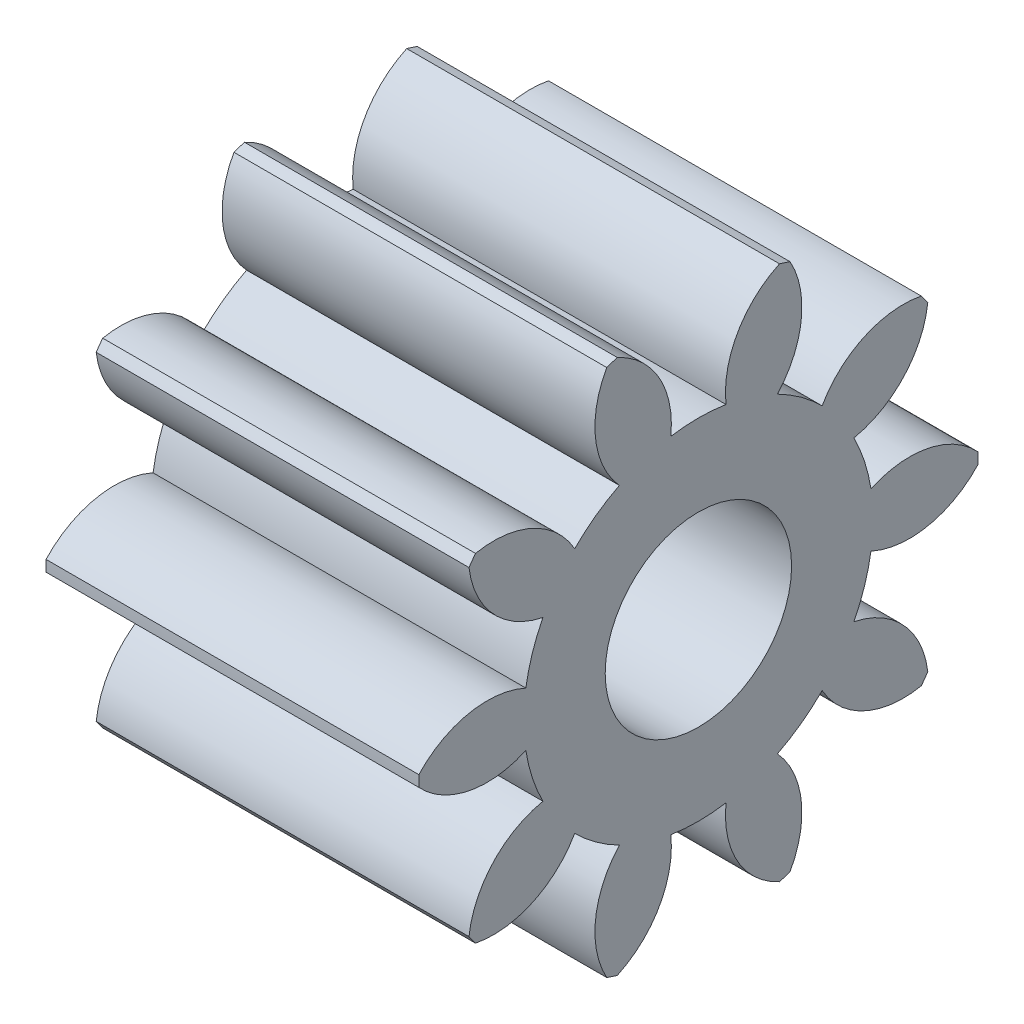
SolidWorks part; units mm, degrees
ref_plane "Plane1" through (0, 0, 0) normal (0, 0, 1) x (1, 0, 0)
ref_plane "Plane2" through (0, 0, 0) normal (0, 1, 0) x (1, 0, 0)
ref_plane "Plane3" through (0, 0, 0) normal (1, 0, 0) x (0, 0, -1)
sketch "HoldingSke" plane through (0, 0, 0) normal (0, 1, 0) x (1, 0, 0)
  line L0 (0, 0) -> (1.9696, -0.3473)
  line L1 (-15, 0) -> (100, 0) construction
  line L2 (0, 0) -> (-2.1039, 2.3779)
  line L3 (0, 0) -> (-11.863, 4.5341)
  line L4 (0, 0) -> (8.5048, 1.4996)
  line L5 (0, 0) -> (-46.8476, -17.4728)
  line L6 (0, 0) -> (-2.9014, -1.9576)
  line L7 (-2.1039, 2.3779) -> (8.6586, 51.2059)
  line L8 (-76.2, 54.61) -> (-75.9, 54.61)
  line L9 (-71.009, 38.7566) -> (-53.1078, 45.2721)
  line L10 (-76.2, 71.12) -> (104.1128, 71.12)
  line L11 (0, 0) -> (-3.5, 0)
  line L12 (-76.2, 101.6) -> (-76.181, 101.6)
  line L13 (24.9733, 27.94) -> (52.9518, 28.4284)
  line L14 (24.9733, 27.94) -> (24.9743, 27.94)
  line L15 (24.9733, 27.94) -> (100.4006, 29.5858)
  line L16 (-63.627, -0.5) -> (-12.827, -0.5)
  circle A0 centre (0, 0) radius 1
  circle A1 centre (0, 0) radius 1.874
  circle A2 centre (0, 0) radius 37.5
  circle A3 centre (0, 0) radius 1
  dimension "Num_teeth" = 10
  dimension "Pitch_radius" = 180.3128
  dimension "Width" = 3.5
sketch "BasProSke" plane through (0, 0, 0) normal (0, 1, 0) x (1, 0, 0)
  line L0 (-10, 0) -> (60, 0) construction
  line L1 (0, 0) -> (0, 3)
  line L2 (0, 0) -> (4, 0)
  line L3 (4, 0) -> (4, 3)
  line L4 (4, 3) -> (0, 3)
  dimension "Thickness" = 4
  dimension "Diameter" = 6
revolve "Base-Revolve" add sketch "BasProSke" angle 360 about L0
sketch "TooCutSke" plane through (0, 0, 0) normal (1, 0, 0) x (0, 0, -1)
  line L1 (0, 0) -> (0, 107) construction
  line L2 (0, 0) -> (-0.4243, 2.4637) construction
  line L3 (0, 0) -> (-1.5292, 4.7063) construction
  line L4 (-0.4243, 2.4637) -> (-0.7646, 2.3532) construction
  arc A0 (0.2964, 1.8504) -> (-0.2964, 1.8504) centre (0, 0) ccw
  arc A1 (0.9059, 2.8866) -> (-0.9059, 2.8866) centre (0, 0) ccw
  circle A2 centre (0, 0) radius 2.5 construction
  circle A3 centre (0, 0) radius 2.3492 construction
  arc A4 (-0.2964, 1.8504) -> (-0.9059, 2.8866) centre (-1.2901, 1.9633) ccw
  arc A5 (0.9059, 2.8866) -> (0.2964, 1.8504) centre (1.2901, 1.9633) ccw
extrude "ToothCut" cut sketch "TooCutSke" along normal through all
fillet "Breaks" [suppressed] radius 0.01 tangent propagation no
fillet "RootFillets" [suppressed] radius 0.126
pattern_circular "TeethCuts" count 10 every 36 about axis through (-10, 0, 0) along (1, 0, 0) of "ToothCut", "RootFillets", "Breaks"
sketch "HubNeaOneSke" plane through (0, 0, 0) normal (-1, 0, 0) x (0, 0, 1)
  circle A0 centre (0, 0) radius 1.874
  dimension "Diameter" = 3.748
extrude "HubNearOne" [suppressed] add sketch "HubNeaOneSke" along normal blind 46.0001
sketch "HubNeaBotSke" plane through (0, 0, 0) normal (-1, 0, 0) x (0, 0, 1)
  circle A0 centre (0, 0) radius 1.874
  dimension "Diameter" = 3.748
extrude "HubNearBoth" [suppressed] add sketch "HubNeaBotSke" along normal blind 23
ref_plane "FarPln" through (4, 0, 0) normal (1, 0, 0) x (0, 0, -1)
sketch "HubFarSke" plane through (4, 0, 0) normal (1, 0, 0) x (0, 0, -1)
  circle A0 centre (0, 0) radius 1.874
  dimension "Diameter" = 3.748
extrude "HubFar" [suppressed] add sketch "HubFarSke" along normal blind 23
sketch "BorSke" plane through (0, 0, 0) normal (1, 0, 0) x (0, 0, -1)
  circle A0 centre (0, 0) radius 1
  dimension "Diameter" = 2
extrude "Bore" cut sketch "BorSke" along normal mid plane 100.0001
sketch "KeySke" plane through (0, 0, 0) normal (1, 0, 0) x (0, 0, -1)
  line L0 (-0.4, 0) -> (-0.4, 1.3)
  line L1 (-0.4, 1.3) -> (0.4, 1.3)
  line L2 (0.4, 1.3) -> (0.4, 0)
  line L3 (0, 0) -> (0, 34) construction
  line L4 (-0.4, 0) -> (0.4, 0)
  dimension "Width" = 0.8
extrude "Keyway" [suppressed] cut sketch "KeySke" along normal mid plane 100.0001
pattern_circular "Keyway2" [suppressed] count 2 every 90 about axis through (-10, 0, 0) along (1, 0, 0) reverse direction yes
equation "' \"Module@HoldingSke\" = 6.35"
equation "' \"Num_teeth@HoldingSke\" = 12"
equation "' \"Ap@HoldingSke\" =  20"
equation "' \"Ap@HoldingSke\" = 20"
equation "' \"Width@HoldingSke\" = 0.5 * 25.4"
equation "' \"Hub_dia@HoldingSke\"= 1 * 25.4"
equation "' \"Hub_dia@HoldingSke\" = 1 * 25.4"
equation "' \"Overall_len@HoldingSke\" = 1.0 * 25.4"
equation "' \"Bore@HoldingSke\" = 0.75 * 25.4"
equation "' \"T_dim@HoldingSke\" = 0.1 * 25.4"
equation "' \"Width@KeySke\" = 0.25 * 25.4"
equation "' \"Show_teeth@HoldingSke\" = 13"
equation "' \"Backlash@HoldingSke\" = 0.009 * 25.4"
equation "' \"Addendum_fac@HoldingSke\" = 1.0"
equation "' \"Dedendum_fac@HoldingSke\" = 1.25"
equation "' \"Dedendum_add@HoldingSke\" = 0.00005 * 25.4"
equation "' \"Clearance_fac@HoldingSke\" = 0.25"
equation "\"Pitch@HoldingSke\" = 1 / \"Module@HoldingSke\""
equation "\"Overcut_dia@TooCutSke\" = (\"Num_teeth@HoldingSke\" + 2 * \"Addendum_fac@HoldingSke\") / \"Pitch@HoldingSke\" + 0.002 * 25.4"
equation "\"Pitch_dia@TooCutSke\" = \"Num_teeth@HoldingSke\" / \"Pitch@HoldingSke\""
equation "\"Base_dia@TooCutSke\" = \"Num_teeth@HoldingSke\" / \"Pitch@HoldingSke\" * cos((\"Ap@HoldingSke\"  * 3.14159265 / 180))"
equation "\"Root_dia@TooCutSke\" = (\"Num_teeth@HoldingSke\" + 2) / \"Pitch@HoldingSke\" - 2 * (\"Addendum_fac@HoldingSke\" + \"Dedendum_fac@HoldingSke\") / \"Pitch@HoldingSke\" - \"Dedendum_add@HoldingSke\" * 2"
equation "\"Half_ang@TooCutSke\" = 180 / \"Num_teeth@HoldingSke\""
equation "\"Half_CT@TooCutSke\" = \"Num_teeth@HoldingSke\" / \"Pitch@HoldingSke\" * sin((3.14159265 / 2 / \"Num_teeth@HoldingSke\")) / 2 - 7 * \"Backlash@HoldingSke\" / 4"
equation "\"Flank_rad@TooCutSke\" = \"Num_teeth@HoldingSke\" / \"Pitch@HoldingSke\" / 5"
equation "\"Radius@RootFillets\" = \"Clearance_fac@HoldingSke\" / \"Pitch@HoldingSke\" + \"Dedendum_add@HoldingSke\""
equation "\"Break_rad@Breaks\" = 0.02 / \"Pitch@HoldingSke\""
equation "\"Thickness@HoldingSke\" = \"Width@HoldingSke\""
equation "\"OAL@HoldingSke\" = \"Thickness@HoldingSke\""
equation "\"MHD@HoldingSke\" = (\"Num_teeth@HoldingSke\" + 2) / \"Pitch@HoldingSke\" - 2 * (\"Addendum_fac@HoldingSke\" + \"Dedendum_fac@HoldingSke\")  / \"Pitch@HoldingSke\" - \"Dedendum_add@HoldingSke\" * 2"
equation "\"MBD@HoldingSke\" = (\"Num_teeth@HoldingSke\" + 2) / \"Pitch@HoldingSke\" - 2 * (\"Addendum_fac@HoldingSke\" + \"Dedendum_fac@HoldingSke\")  / \"Pitch@HoldingSke\" - \"Dedendum_add@HoldingSke\" * 2 - 0.002 * 25.4"
equation "\"MHD@HoldingSke\" = ((sgn( \"MHD@HoldingSke\" - \"Hub_dia@HoldingSke\" )-1)*( \"MHD@HoldingSke\" - \"Hub_dia@HoldingSke\" ))/-2+ \"Hub_dia@HoldingSke\""
equation "\"MBD@HoldingSke\" = ((sgn( \"MBD@HoldingSke\" - \"Bore@HoldingSke\" )-1)*( \"MBD@HoldingSke\" - \"Bore@HoldingSke\" ))/-2+ \"Bore@HoldingSke\""
equation "\"OAL@HoldingSke\" = ((sgn( \"OAL@HoldingSke\" - \"Overall_len@HoldingSke\" )+1)*( \"OAL@HoldingSke\" - \"Overall_len@HoldingSke\" ))/2 + \"Overall_len@HoldingSke\" + 0.000002 * 25.4"
equation "\"Num_teeth@TeethCuts\" = int( \"Show_teeth@HoldingSke\" ) + 1"
equation "\"Num_teeth@TeethCuts\" = ((sgn( \"Num_teeth@TeethCuts\" - \"Num_teeth@HoldingSke\" )-1)*( \"Num_teeth@TeethCuts\" - \"Num_teeth@HoldingSke\" ))/-2+ \"Num_teeth@HoldingSke\""
equation "\"Num_teeth@TeethCuts\" = ((sgn( \"Num_teeth@TeethCuts\" - 2.0)+1)*( \"Num_teeth@TeethCuts\" - 2.0))/2 +2.0"
equation "\"Angle@TeethCuts\" = 360.0 / \"Num_teeth@HoldingSke\""
equation "\"Diameter@BasProSke\" = (\"Num_teeth@HoldingSke\" + 2 * \"Addendum_fac@HoldingSke\") / \"Pitch@HoldingSke\""
equation "\"Thickness@BasProSke\"=\"Thickness@HoldingSke\"+0.5"
equation "' \"Fillet_rad@BasProSke\" =  \"Thickness@HoldingSke\" * 0.05"
equation "' \"Fillet_rad@BasProSke\" = \"Thickness@HoldingSke\" * 0.05"
equation "\"MHD@HoldingSke\" = ((sgn( \"MHD@HoldingSke\" - \"Root_dia@TooCutSke\" )-1)*( \"MHD@HoldingSke\" - \"Root_dia@TooCutSke\" ))/-2+ \"Root_dia@TooCutSke\""
equation "\"Diameter@HubNeaOneSke\" = \"MHD@HoldingSke\""
equation "\"Length@HubNearOne\" = \"OAL@HoldingSke\" - \"Thickness@BasProSke\""
equation "\"Diameter@HubNeaBotSke\" = \"MHD@HoldingSke\""
equation "\"Length@HubNearBoth\" = ( \"OAL@HoldingSke\" - \"Thickness@BasProSke\" ) / 2.0"
equation "\"Thickness@FarPln\" = \"Thickness@BasProSke\""
equation "\"Diameter@HubFarSke\" = \"MHD@HoldingSke\""
equation "\"Length@HubFar\" = ( \"OAL@HoldingSke\" - \"Thickness@BasProSke\" ) / 2.0"
equation "\"Diameter@BorSke\" = \"MBD@HoldingSke\""
equation "\"D1@Bore\" = \"OAL@HoldingSke\" * 2.0"
equation "\"D1@Keyway\" = \"OAL@HoldingSke\" * 2.0"
equation "\"Offset@KeySke\" = \"T_dim@HoldingSke\" + \"MBD@HoldingSke\" / 2.0"
